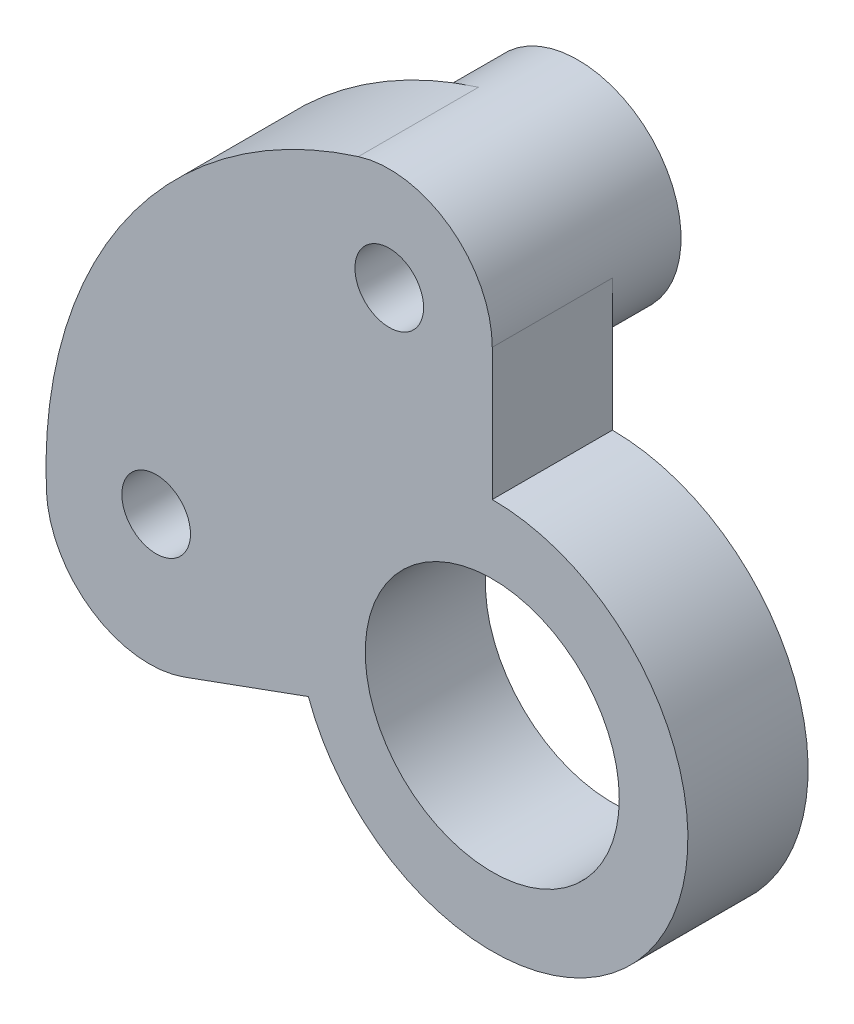
SolidWorks part; units mm, degrees
ref_plane "Front Plane" through (0, 0, 0) normal (0, 0, 1) x (1, 0, 0)
ref_plane "Top Plane" through (0, 0, 0) normal (0, 1, 0) x (1, 0, 0)
ref_plane "Right Plane" through (0, 0, 0) normal (1, 0, 0) x (0, 0, -1)
sketch "Sketch1" plane through (0, 0, 0) normal (0, 0, 1) x (1, 0, 0)
  circle A0 centre (0, 0) radius 3.7
  circle A1 centre (0, 0) radius 5.7
  circle A2 centre (0, 0) radius 13
  dimension "D1" = 7.4
  dimension "D2" = 2
  dimension "D3" = 26
extrude "Boss-Extrude1" add sketch "Sketch1" along normal blind 3.5 contours A1 A0 | A2 A1 region at (-5.5388, 0, 0) region at (-12.6323, 0, 0)
sketch "Sketch2" plane through (0, 0, 3.5) normal (0, 0, 1) x (1, 0, 0)
  line L0 (0, 0) -> (-12.216, -4.4463)
  line L1 (0, 0) -> (0, 13)
  circle A2 centre (0, 0) radius 13
  circle A3 centre (0, 0) radius 13
  circle A4 centre (0, 0) radius 13
  circle A5 centre (0, 0) radius 5.7
  circle A6 centre (0, 0) radius 5.7
  circle A7 centre (0, 0) radius 3.7
  circle A8 centre (0, 0) radius 3.7
  circle M9 centre (0, 0) radius 13
  dimension "D5" = 250
  dimension "D2" = 0
  dimension "D3" = 0
  dimension "D4" = 0
extrude "Cut-Extrude1" cut sketch "Sketch2" against normal blind 10 contours A6 L0 L1 M9 region at (1.0527, -5.9701, 3.5)
sketch "Sketch3" plane through (0, 0, 3.5) normal (0, 0, 1) x (1, 0, 0)
  line L0 (0, 5.7) -> (0, 13) construction
  circle A0 centre (-3, 9.5394) radius 1
  dimension "D1" = 2
  dimension "D3" = 3
  dimension "D2" = 10
extrude "Cut-Extrude2" cut sketch "Sketch3" against normal blind 10
sketch "Sketch5" plane through (0, 0, 3.5) normal (0, 0, 1) x (1, 0, 0)
  line L0 (-3, 9.5394) -> (0, 0) construction
  line L1 (0, 0) -> (-9.7904, 0.4347) construction
  circle A0 centre (-9.7904, 0.4347) radius 1
  circle A1 centre (-3, 9.5394) radius 1 construction
  circle A2 centre (-3, 9.5394) radius 1 construction
  dimension "D2" = 2
  dimension "D3" = 70
  dimension "D1" = 9.8
extrude "Cut-Extrude3" cut sketch "Sketch5" against normal blind 6
fillet "Fillet1" radius 3 2 edges at (-12.216, -4.4463, 1.75) (0, 13, 1.75)
sketch "Sketch6" plane through (0, 0, 0) normal (0, 0, -1) x (-1, 0, 0)
  circle A0 centre (9.7904, 0.4347) radius 3
  circle A1 centre (3, 9.5394) radius 3
  circle A2 centre (9.7904, 0.4347) radius 1 construction
  circle A3 centre (3, 9.5394) radius 1 construction
  circle A4 centre (9.7904, 0.4347) radius 1
  circle A5 centre (3, 9.5394) radius 1
  circle M4 centre (9.7904, 0.4347) radius 1
  circle M5 centre (3, 9.5394) radius 1
  dimension "D1" = 6
extrude "Boss-Extrude2" add sketch "Sketch6" along normal blind 0.5 contours A0 M4 region at (-6.8752, 0.4347, 0)
extrude "Boss-Extrude3" add sketch "Sketch6<3>" along normal blind 2 contours A1 M5 region at (-0.0849, 9.5394, 0)
sketch "Sketch6<3>" plane through (0, 0, 0) normal (0, 0, -1) x (-1, 0, 0) same geometry as "Sketch6"
